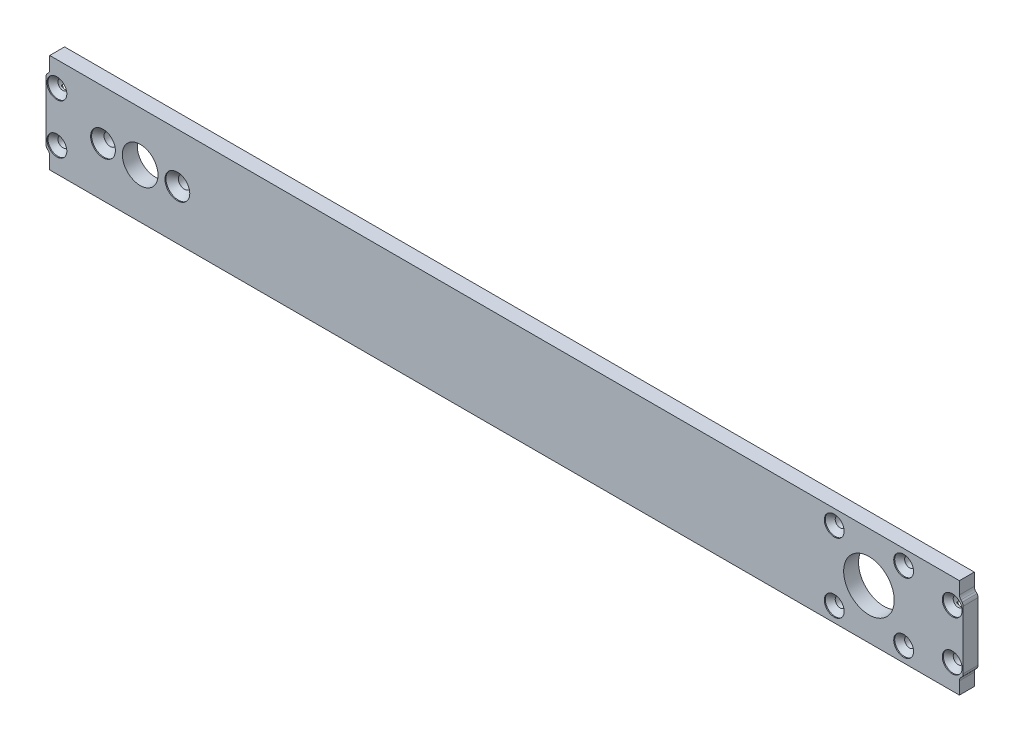
SolidWorks part; units mm, degrees
ref_plane "Front Plane" through (0, 0, 0) normal (0, 0, 1) x (1, 0, 0)
ref_plane "Top Plane" through (0, 0, 0) normal (0, 1, 0) x (1, 0, 0)
ref_plane "Right Plane" through (0, 0, 0) normal (1, 0, 0) x (0, 0, -1)
sketch "Sketch1" plane through (0, 0, 0) normal (0, 0, 1) x (1, 0, 0)
  line L1 (-92.5, 10) -> (92.5, 10)
  line L2 (-92.5, 10) -> (-92.5, -10)
  line L3 (-92.5, -10) -> (92.5, -10)
  line L4 (92.5, 10) -> (92.5, -10)
  line L5 (-92.5, 10) -> (92.5, -10) construction
  line L6 (-92.5, -10) -> (92.5, 10) construction
  point P0 (0, 0)
  dimension "D1" = 20
  dimension "D2" = 185
extrude "Base shape" add sketch "Sketch1" against normal blind 3
sketch "Sketch2" plane through (0, 0, 0) normal (0, 0, 1) x (1, 0, 0)
  line L0 (-83.5, 10) -> (-83.5, -10) construction
  line L1 (92.5, 10) -> (-92.5, 10) construction
  line L2 (-92.5, -10) -> (92.5, -10) construction
  line L3 (-92.5, 10) -> (-92.5, -10) construction
  line L4 (-92.5, 0) -> (92.5, 0) construction
  line L5 (92.5, -10) -> (92.5, 10) construction
  line L6 (-73.5, 10) -> (-73.5, -10) construction
  line L7 (0, 10) -> (0, -10) construction
  line L8 (73.5, 5.1) -> (92.5, 5.1) construction
  line L9 (-73.5, 3.6) -> (-92.5, 3.6) construction
  line L11 (80.5, -7) -> (66.5, -7)
  line L12 (80.5, -7) -> (80.5, 7)
  line L13 (80.5, 7) -> (66.5, 7)
  line L14 (66.5, -7) -> (66.5, 7)
  line L15 (80.5, -7) -> (66.5, 7) construction
  line L16 (80.5, 7) -> (66.5, -7) construction
  circle A0 centre (-73.5, 0) radius 10
  circle A1 centre (-81, 0) radius 1.25
  circle A2 centre (-66, 0) radius 1.25
  circle A3 centre (-73.5, 0) radius 3.6
  circle A4 centre (73.5, 0) radius 5.1
  circle A5 centre (66.5, 7) radius 1
  circle A6 centre (80.5, 7) radius 1
  circle A7 centre (80.5, -7) radius 1
  circle A8 centre (66.5, -7) radius 1
  dimension "D2" = 20
  dimension "D3" = 2.5
  dimension "D4" = 15
  dimension "D5" = 7.2
  dimension "D6" = 10.2
  dimension "D8" = 2
  dimension "D1" = 147
  dimension "D7" = 14
extrude "Motor cutouts" cut sketch "Sketch2" against normal up to next contours A5 | A6 | A7 | A8 | A1 | A2 | A3 | A4
sketch "Sketch5" plane through (0, 0, -3) normal (0, 0, -1) x (-1, 0, 0)
  line L0 (0, 10) -> (0, -10) construction
  line L3 (-92.5, 10) -> (92.5, 10) construction
  line L4 (92.5, -10) -> (-92.5, -10) construction
  line L5 (-60, -7) -> (60, -7) construction
  line L6 (-60, -6) -> (60, -6)
  line L7 (-60, -8) -> (60, -8)
  arc A0 (-60, -6) -> (-60, -8) centre (-60, -7) ccw
  arc A1 (60, -8) -> (60, -6) centre (60, -7) ccw
  point P8 (0, -7)
  dimension "D1" = 120
  dimension "D2" = 2
  dimension "D3" = 2
extrude "PCB slot" cut sketch "Sketch5" against normal blind 0.775
sketch "Sketch6" plane through (0, 0, 0) normal (0, 0, 1) x (1, 0, 0)
  line L0 (90.3, 10) -> (90.3, -10) construction
  line L1 (92.5, 10) -> (-92.5, 10) construction
  line L2 (-92.5, -10) -> (92.5, -10) construction
  line L3 (92.5, -10) -> (92.5, 10) construction
  line L4 (92.5, 0) -> (-92.5, 0) construction
  line L5 (-92.5, 10) -> (-92.5, -10) construction
  line L6 (0, 10) -> (0, -10) construction
  circle A0 centre (90.3, 5) radius 1
  circle A2 centre (90.3, -5) radius 1
  circle A3 centre (-90.3, -5) radius 1
  circle A5 centre (-90.3, 5) radius 1
  dimension "D2" = 2
  dimension "D1" = 2.2
  dimension "D3" = 10
extrude "End plate holes" cut sketch "Sketch6" against normal up to next
hole_wizard "M2.5 countersunks" positions "Sketch3" profile "Sketch4" countersink size "M2.5" standard "ANSI Metric" end condition through all
sketch "Sketch3" plane through (0, 0, 0) normal (0, 0, 1) x (1, 0, 0)
  point P0 (-81, 0)
  point P3 (-66, 0)
  point P29 (0, 0)
  point P30 (0, 0)
  point P31 (0, 0)
  point P32 (0, 0)
  point P33 (0, 0)
  point P34 (0, 0)
  point P35 (0, 0)
sketch "Sketch4" plane through (-81, 0, 0) normal (1, 0, 0) x (0, -1, 0)
  line L0 (0, 0) -> (0, 3)
  line L1 (0, 3) -> (1.25, 3)
  line L2 (1.25, 3) -> (1.25, 1.45)
  line L3 (1.25, 1.45) -> (2.5, 0.2)
  line L4 (2.5, 0.2) -> (2.5, 0)
  line L6 (2.5, 0) -> (0, 0)
  line L7 (-1.25, 1.45) -> (-2.5, 0.2) construction
  line L11 (0, -6.35) -> (0, 107.95) construction
  dimension "Thru Hole Dia." = 2.5
  dimension "Thru Hole Depth" = 3
  dimension "C'Sink Dia." = 5
  dimension "C'Sink Angle" = 90
  dimension "Head Clearance" = 0.2
hole_wizard "M2 countersunks" positions "Sketch10" profile "Sketch9" countersink size "M2" standard "ANSI Metric" end condition through all
sketch "Sketch10" plane through (0, 0, 0) normal (0, 0, 1) x (1, 0, 0)
  point P2 (90.3, 5)
  point P8 (90.3, -5)
  point P11 (-90.3, 5)
  point P17 (-90.3, -5)
  point P20 (80.5, -7)
  point P23 (66.5, -7)
  point P26 (66.5, 7)
  point P29 (80.5, 7)
sketch "Sketch9" plane through (90.3, 5, 0) normal (1, 0, 0) x (0, -1, 0)
  line L0 (0, 0) -> (0, 3)
  line L1 (0, 3) -> (1, 3)
  line L2 (1, 3) -> (1, 1.2)
  line L3 (1, 1.2) -> (2, 0.2)
  line L4 (2, 0.2) -> (2, 0)
  line L6 (2, 0) -> (0, 0)
  line L7 (-1, 1.2) -> (-2, 0.2) construction
  line L11 (0, -6.35) -> (0, 107.95) construction
  dimension "Thru Hole Dia." = 2
  dimension "Thru Hole Depth" = 3
  dimension "C'Sink Dia." = 4
  dimension "C'Sink Angle" = 90
  dimension "Head Clearance" = 0.2
sketch "Sketch12" plane through (0, 0, -3) normal (0, 0, -1) x (-1, 0, 0)
  line L0 (-92.5, 0) -> (92.5, 0) construction
  line L1 (-92.5, -10) -> (-92.5, 10) construction
  line L2 (92.5, 10) -> (92.5, -10) construction
  line L3 (-90.3, 5) -> (-90.3, -5) construction
  line L4 (-88.7, 4.05) -> (-91.9, 0.85) construction
  line L5 (-91.9, 4.05) -> (-88.7, 4.05)
  line L6 (-91.9, 4.05) -> (-91.9, -4.05)
  line L7 (-91.9, -4.05) -> (-88.7, -4.05)
  line L8 (-88.7, 4.05) -> (-88.7, -4.05)
  line L9 (-91.9, 4.05) -> (-88.7, -4.05) construction
  line L10 (-91.9, -4.05) -> (-88.7, 4.05) construction
  line L11 (0, 10) -> (0, -10) construction
  line L12 (-92.5, 10) -> (92.5, 10) construction
  line L13 (92.5, -10) -> (-92.5, -10) construction
  line L14 (91.9, -4.05) -> (88.7, -4.05)
  line L15 (91.9, 4.05) -> (88.7, 4.05)
  line L16 (91.9, 4.05) -> (91.9, -4.05)
  line L17 (88.7, 4.05) -> (88.7, -4.05)
  line L18 (-91.1929, 4.3429) -> (-89.4071, 4.3429)
  line L19 (-91.1929, -4.3429) -> (-89.4071, -4.3429)
  line L20 (91.1929, 4.3429) -> (89.4071, 4.3429)
  line L21 (91.1929, -4.3429) -> (89.4071, -4.3429)
  circle A0 centre (-89.4071, 3.3429) radius 1
  circle A1 centre (-91.1929, 3.3429) radius 1
  circle A2 centre (-89.4071, -3.3429) radius 1
  circle A3 centre (-91.1929, -3.3429) radius 1
  circle A4 centre (89.4071, -3.3429) radius 1
  circle A5 centre (91.1929, -3.3429) radius 1
  circle A6 centre (89.4071, 3.3429) radius 1
  circle A7 centre (91.1929, 3.3429) radius 1
  point P10 (-90.3, 0)
  circle M9 centre (-90.3, -5) radius 1
  circle M10 centre (90.3, -5) radius 1
  circle M11 centre (90.3, 5) radius 1
  circle M12 centre (-90.3, 5) radius 1
  dimension "D3" = 2
  dimension "D1" = 3.2
  dimension "D2" = 8.1
  dimension "D4" = 45
extrude "Tap slots" cut sketch "Sketch12" against normal blind 1.4 contours A1 L5 A0 L18 M12 | A3 L19 A2 L7 M9 | A7 L20 A6 L15 M11 | A5 L14 A4 L21 M10 | A1 | A0 | A2 | A3 | L6 L7 L8 L5 | A6 | A7 | A5 | A4 | L17 L14 L16 L15 region at (90.3, 4.2292, -3) region at (90.3, -4.2292, -3) region at (-90.3, -4.2292, -3) region at (-90.3, 4.2292, -3)
sketch "Sketch13" plane through (0, 0, 0) normal (0, 0, 1) x (1, 0, 0)
  line L0 (-92.5, -10) -> (92.5, -10) construction
  line L1 (-92.5, 10) -> (-91.75, 10)
  line L2 (-92.5, 10) -> (-92.5, -10)
  line L3 (-92.5, -10) -> (-91.75, -10)
  line L4 (-91.75, 10) -> (-91.75, -10)
  line L5 (-92.5, 0) -> (92.5, 0) construction
  line L6 (92.5, -10) -> (92.5, 10) construction
  line L7 (0, 10) -> (0, -10) construction
  line L8 (92.5, 10) -> (-92.5, 10) construction
  line L9 (92.5, -10) -> (91.75, -10)
  line L10 (91.75, 10) -> (91.75, -10)
  line L11 (92.5, 10) -> (91.75, 10)
  line L12 (92.5, 10) -> (92.5, -10)
  circle A0 centre (-90.3, 5) radius 2.5
  circle A1 centre (-90.3, -5) radius 2.5
  circle A2 centre (90.3, 5) radius 2.5
  circle A3 centre (90.3, -5) radius 2.5
  line M16 (92.5, -10) -> (92.5, 10)
  line M17 (92.5, 10) -> (-92.5, 10)
  line M18 (-92.5, 10) -> (-92.5, -10)
  line M19 (-92.5, -10) -> (92.5, -10)
  dimension "D2" = 5
  dimension "D1" = 0.75
extrude "Cut-Extrude3" cut sketch "Sketch13" against normal up to next contours A0 L4 M17 M18 | A1 L4 M18 M19 | L10 A2 M16 M17 | A3 L10 M16 M19 region at (-92.1406, 8.3301, 0) region at (92.1406, 8.3301, 0) region at (-92.1406, -8.3301, 0) region at (92.1406, -8.3301, 0)
fillet "Fillet1" radius 1 8 edges at (-91.75, -7.0365, -1.5) (-92.5, -6.1874, -1.5) (-92.5, 6.1874, -1.5) (-91.75, 7.0365, -1.5) (92.5, 6.1874, -1.5) (91.75, 7.0365, -1.5) (92.5, -6.1874, -1.5) (91.75, -7.0365, -1.5)
